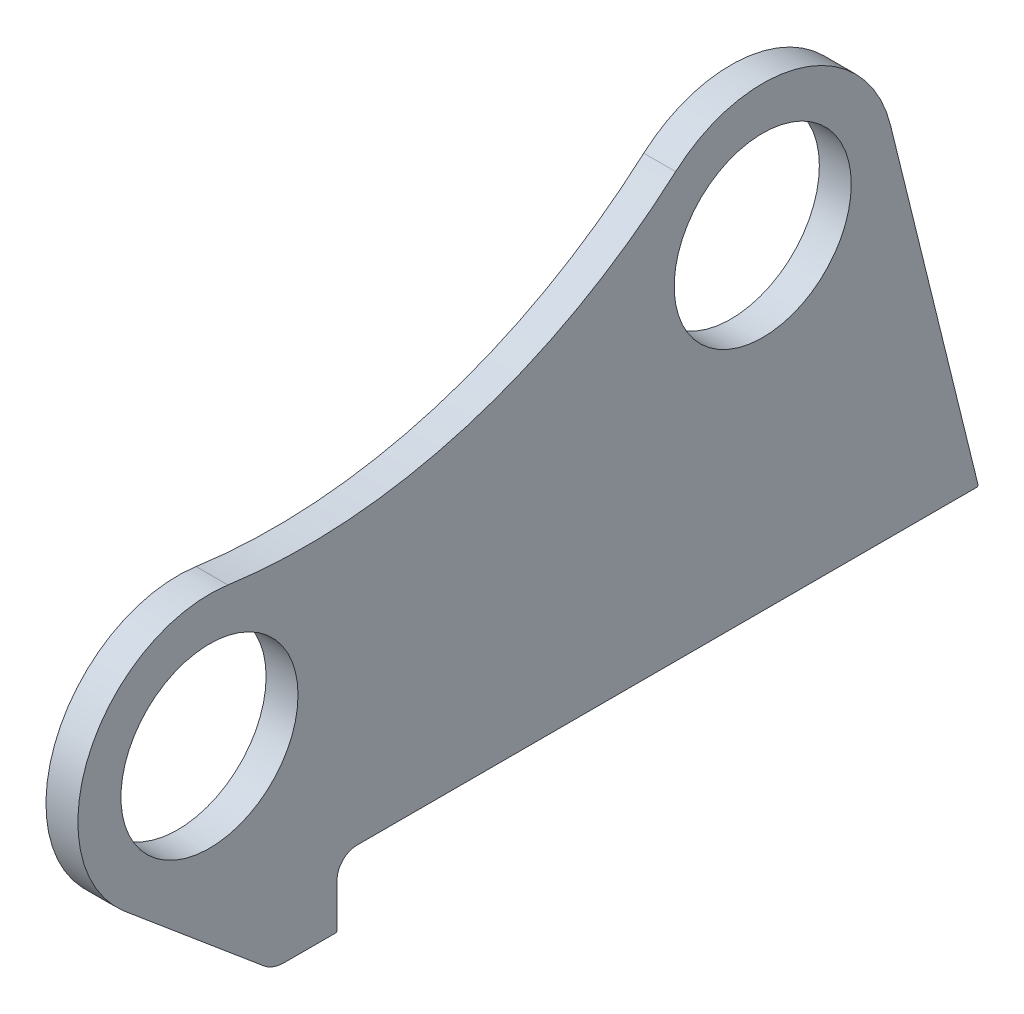
SolidWorks part; units mm, degrees
material "MS-Grade 350"
ref_plane "Front Plane" through (0, 0, 0) normal (0, 0, 1) x (1, 0, 0)
ref_plane "Top Plane" through (0, 0, 0) normal (0, 1, 0) x (1, 0, 0)
ref_plane "Right Plane" through (0, 0, 0) normal (1, 0, 0) x (0, 0, -1)
sketch "Sketch1" plane through (0, 0, 0) normal (1, 0, 0) x (0, 0, -1)
  line L0 (0, -41) -> (0, -12.5)
  line L1 (12.5, 0) -> (402, 0)
  line L3 (402, 0) -> (346.8796, 223.6178)
  line L4 (-133.0582, 36.825) -> (-45.9722, -36.3151)
  line L11 (0, -41) -> (-33.1096, -41)
  line L12 (-80, 100) -> (266.7772, 203.873) construction
  circle A0 centre (-80, 100) radius 55.5
  circle A1 centre (266.7772, 203.873) radius 55.5
  arc A2 (-68.4259, 181.6841) -> (-133.0582, 36.825) centre (-80, 100) ccw
  arc A4 (-45.9722, -36.3151) -> (-33.1096, -41) centre (-33.1096, -21) ccw
  arc A5 (0, -12.5) -> (12.5, 0) centre (12.5, -12.5) cw
  arc A9 (346.8796, 223.6178) -> (212.203, 265.7432) centre (266.7772, 203.873) ccw
  arc A10 (-68.4259, 181.6841) -> (212.203, 265.7432) centre (-19.3235, 528.2226) ccw
  point P31 (0, 0)
  dimension "D2" = 100
  dimension "D4" = 82.5
  dimension "D5" = 111
  dimension "D6" = 41
  dimension "D7" = 350
  dimension "D13" = 40.026
  dimension "D20" = 12.5
  dimension "D3" = 20
  dimension "D12" = 402
  dimension "D15" = 16.675
  dimension "D16" = 362
  dimension "D17" = 80
sheet metal parameters "Sheet-Metal1" thickness 20 parameters "D1"=92
base flange "Base-Flange1" sketch "Sketch1" thickness 20 reverse thickness direction no parameters "D1"=92
fillet "Fillet-1.0" radius 1 2 edges at (-10, 0, -402) (-10, -41, 0)
flat pattern "Flat-Pattern1" [suppressed]
sketch "Bend-Lines1" plane through (0, 0, 0) normal (0, 1, 0) x (1, 0, 0)
sketch3d "Bounding-Box1" [suppressed]
  line L0 (-159.6299, -579.154, 0) -> (414.8787, -520.584, 0) construction
  line L1 (-191.1408, -270.0661, 0) -> (383.3678, -211.4961, 0) construction
  line L2 (-159.6299, -579.154, 0) -> (-191.1408, -270.0661, 0) construction
  line L3 (414.8787, -520.584, 0) -> (383.3678, -211.4961, 0) construction
